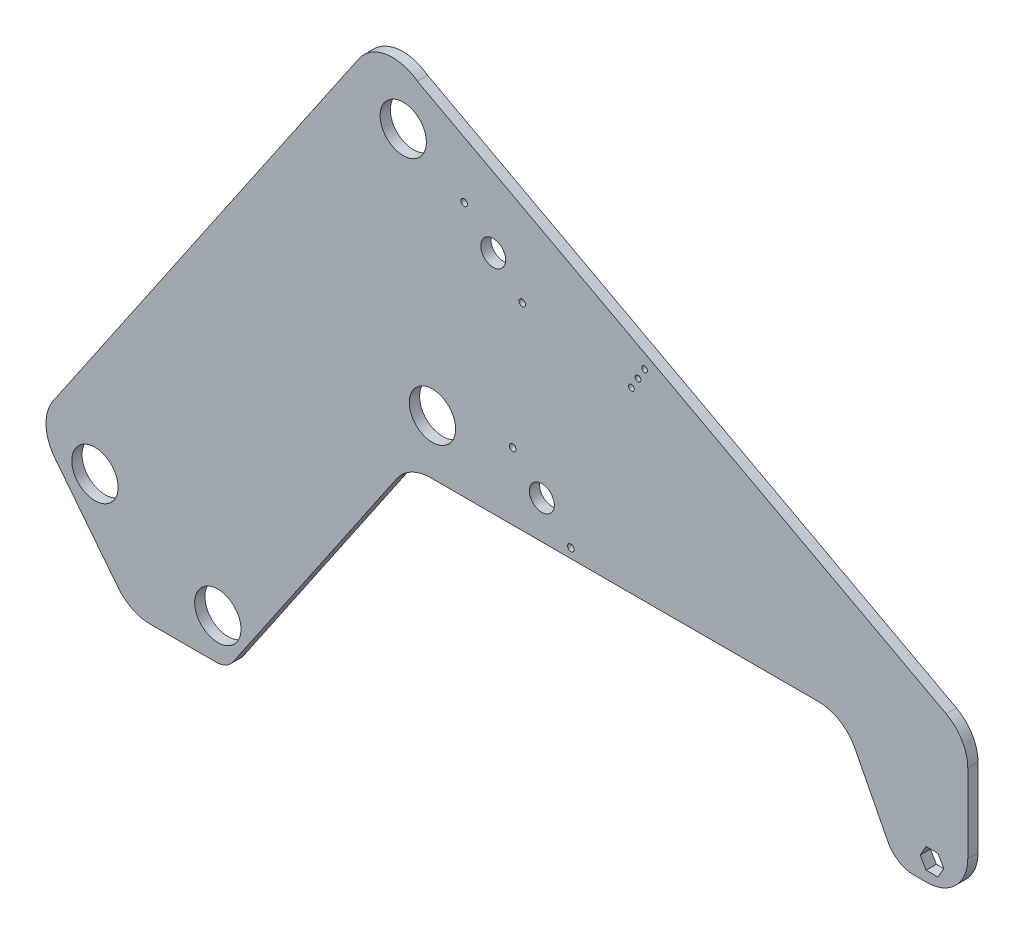
SolidWorks part; units mm, degrees
other "Markup1"
sketch "Sketch1" plane through (-441.7893, 331.8239, 6.35) normal (-0.0431, 0.0102, 0.999) x (0.9985, 0.0354, 0.0427)
sketch "Sketch2" plane through (-413.6701, 343.933, 6.35) normal (-0.0431, 0.0102, 0.999) x (0.9985, 0.0354, 0.0427)
sketch "Sketch3" plane through (-436.3774, 318.5567, 6.35) normal (-0.0431, 0.0102, 0.999) x (0.9985, 0.0354, 0.0427)
sketch "Sketch5" plane through (-436.3774, 318.5567, 6.35) normal (-0.0431, 0.0102, 0.999) x (0.9985, 0.0354, 0.0427)
sketch "Sketch7" plane through (-430.3226, 318.5567, 6.35) normal (-0.0431, 0.0102, 0.999) x (0.9985, 0.0354, 0.0427)
sketch "Sketch9" plane through (-430.3226, 318.5567, 6.35) normal (-0.0431, 0.0102, 0.999) x (0.9985, 0.0354, 0.0427)
sketch "Sketch11" plane through (-430.3226, 318.5567, 6.35) normal (-0.0431, 0.0102, 0.999) x (0.9985, 0.0354, 0.0427)
sketch "Sketch13" plane through (-430.3226, 318.5567, 6.35) normal (-0.0431, 0.0102, 0.999) x (0.9985, 0.0354, 0.0427)
other "Markup2"
sketch "Sketch4" plane through (102.4721, 318.5567, 6.35) normal (0.9364, 0.1073, 0.3342) x (0.3416, -0.0598, -0.9379)
sketch "Sketch6" plane through (102.4721, 318.5567, 6.35) normal (0.9364, 0.1073, 0.3342) x (0.3416, -0.0598, -0.9379)
sketch "Sketch8" plane through (141.2086, 318.5567, 6.35) normal (0.9364, 0.1073, 0.3342) x (0.3416, -0.0598, -0.9379)
sketch "Sketch10" plane through (141.2086, 318.5567, 6.35) normal (0.9364, 0.1073, 0.3342) x (0.3416, -0.0598, -0.9379)
sketch "Sketch12" plane through (141.2086, 318.5567, 6.35) normal (0.9364, 0.1073, 0.3342) x (0.3416, -0.0598, -0.9379)
sketch "Sketch14" plane through (141.2086, 318.5567, 6.35) normal (0.9364, 0.1073, 0.3342) x (0.3416, -0.0598, -0.9379)
material "Lexan"
ref_plane "Front Plane" through (0, 0, 0) normal (0, 0, 1) x (1, 0, 0)
ref_plane "Top Plane" through (0, 0, 0) normal (0, 1, 0) x (1, 0, 0)
ref_plane "Right Plane" through (0, 0, 0) normal (1, 0, 0) x (0, 0, -1)
sketch "Model" plane through (0, 0, 0) normal (0, 0, 1) x (1, 0, 0)
  line L1 (-191.9011, 104.6502) -> (-112.96, 104.6502)
  line L3 (-314.2383, -55.3595) -> (-212.8994, 93.5413)
  line L4 (-236.3088, 307.4396) -> (-425.9253, 28.8296)
  line L5 (-424.901, -1.1522) -> (-385.5815, -51.2048)
  line L13 (126.3831, 53.8502) -> (122.717, 60.2002)
  line L14 (122.717, 60.2002) -> (115.3846, 60.2002)
  line L15 (115.3846, 60.2002) -> (111.7185, 53.8502)
  line L16 (111.7185, 53.8502) -> (115.3846, 47.5002)
  line L17 (115.3846, 47.5002) -> (122.717, 47.5002)
  line L18 (122.717, 47.5002) -> (126.3831, 53.8502)
  line L19 (-365.6075, -60.914) -> (-324.7375, -60.914)
  line L20 (-871.0211, -88.854) -> (370.1019, -88.854) construction
  line L22 (141.2086, 66.5502) -> (141.2086, 78.8846)
  line L27 (107.6196, 41.1502) -> (115.8086, 41.1502)
  line L28 (-399.9752, 2.586) -> (-323.7752, -35.514) construction
  line L29 (-323.7752, -35.514) -> (-190.7071, 138.5169) construction
  line L30 (-190.7071, 138.5169) -> (-208.8329, 283.4378) construction
  line L31 (-208.8329, 283.4378) -> (-399.9752, 2.586) construction
  line L32 (91.8004, 50.8135) -> (71.26, 90.8456)
  line L33 (48.6612, 104.6502) -> (-11.3966, 104.6502)
  line L34 (141.2086, 78.8846) -> (141.2086, 115.3033)
  line L35 (127.8091, 137.6897) -> (-86.3327, 252.4836)
  line L36 (-171.0363, 260.7567) -> (-135.0085, 260.7567) construction
  line L37 (-135.0085, 260.7567) -> (-135.0085, 224.9427)
  line L38 (-171.0363, 260.7567) -> (-135.0085, 224.9427)
  line L39 (-171.0363, 260.7567) -> (-153.0224, 260.7567)
  line L40 (-68.51, 104.6502) -> (-2.1388, 104.6502)
  line L41 (-122.3008, 271.7648) -> (-200.0053, 313.4195)
  line L42 (-122.3008, 271.7648) -> (-86.3327, 252.4836)
  line L43 (-112.96, 104.6502) -> (-68.51, 104.6502)
  line L44 (-153.0224, 260.7567) -> (-153.0224, 244.7547)
  line L45 (-140.9024, 144.2514) -> (-104.8747, 144.2514) construction
  line L46 (-104.8747, 144.2514) -> (-104.8747, 108.4374)
  line L47 (-140.9024, 144.2514) -> (-104.8747, 108.4374)
  line L48 (-140.9024, 144.2514) -> (-122.8885, 144.2514)
  line L49 (-122.8885, 144.2514) -> (-122.8885, 128.2494)
  line L50 (-200.0053, 313.4195) -> (-58.2414, 230.7964)
  line L51 (-58.2414, 230.7964) -> (-55.4813, 235.9452)
  line L52 (-60.5805, 226.7863) -> (-58.2414, 230.7964)
  arc A3 (121.2475, 59.8082) -> (121.352, 60.2002) centre (96.7586, 66.5502) ccw
  circle A9 centre (-323.7752, -35.514) radius 14.351
  circle A10 centre (-399.9752, 2.586) radius 14.351
  circle A12 centre (-190.7071, 138.5169) radius 14.351
  arc A15 (107.6196, 41.1502) -> (91.8004, 50.8135) centre (107.6196, 58.9302) cw
  arc A21 (-191.9011, 104.6502) -> (-212.8994, 93.5413) centre (-191.9011, 79.2502) ccw
  circle A22 centre (-208.8329, 283.4378) radius 14.351
  circle A24 centre (119.0508, 53.8502) radius 6.35 construction
  arc A31 (-324.7375, -60.914) -> (-314.2383, -55.3595) centre (-324.7375, -48.214) ccw
  arc A40 (114.7422, 48.6129) -> (115.0458, 48.9225) centre (96.7586, 66.5502) ccw
  arc A43 (115.8086, 41.1502) -> (141.2086, 66.5502) centre (115.8086, 66.5502) ccw
  arc A44 (-236.3088, 307.4396) -> (-200.0053, 313.4195) centre (-215.3105, 293.1486) cw
  arc A45 (-365.6075, -60.914) -> (-385.5815, -51.2048) centre (-365.6075, -35.514) cw
  arc A46 (71.26, 90.8456) -> (48.6612, 104.6502) centre (48.6612, 79.2502) ccw
  arc A47 (141.2086, 115.3033) -> (127.8091, 137.6897) centre (115.8086, 115.3033) ccw
  arc A48 (-424.901, -1.1522) -> (-425.9253, 28.8296) centre (-404.9271, 14.5386) cw
  circle A51 centre (-171.0363, 262.7887) radius 2.032
  circle A52 centre (-135.0085, 226.9747) radius 2.032
  circle A53 centre (-153.0224, 244.7547) radius 7.747
  circle A54 centre (-140.9024, 146.2834) radius 2.032
  circle A55 centre (-104.8747, 110.4694) radius 2.032
  circle A56 centre (-122.8885, 128.2494) radius 7.747
  circle A57 centre (-59.1373, 229.2606) radius 1.778
  circle A60 centre (-63.2326, 222.2397) radius 1.778
  circle A61 centre (-67.3279, 215.2188) radius 1.778
  ellipse E0 centre (-551.1692, 173.9527) end of major axis (-591.2054, 216.0961) minor radius 17.278
  point P31 (-177.5612, 330.9695)
  point P34 (100.2935, -12.8222)
  point P43 (-377.9543, -60.914)
  point P55 (96.7586, 41.1502)
  point P59 (174.831, 53.8502)
  point P60 (-205.3388, 104.6502)
  point P64 (-436.3829, 13.4639)
  dimension "D3" = 38.1
  dimension "D4" = 104.6502
  dimension "D5" = 76.2
  dimension "D6" = 44.45
  dimension "D7" = 12.7
  dimension "D8" = 28.702
  dimension "D11" = 139.7
  dimension "D12" = 27.94
  dimension "D21" = 124.238
  dimension "D13" = 12.7
  dimension "D16" = 355.6
  dimension "D23" = 25.4
  dimension "D24" = 25.4
  dimension "D26" = 25.4
  dimension "D14" = 406.4
  dimension "D20" = 254
  dimension "D29" = 25.4
  dimension "D31" = 25.4
  dimension "D25" = 88.9
  dimension "D30" = 17.78
  dimension "D32" = 25.4
  dimension "D33" = 25.4
  dimension "D34" = 35.814
  dimension "D35" = 50.8
  dimension "D37" = 4.064
  dimension "D38" = 4.064
  dimension "D39" = 15.494
  dimension "D42" = 4.064
  dimension "D43" = 15.494
  dimension "D44" = 4.064
  dimension "D48" = 3.556
  dimension "D9" = 19.05
  dimension "D10" = 146.05
  dimension "D15" = 33.8667
  dimension "D17" = 339.725
  dimension "D18" = 219.075
  dimension "D19" = 50.8
  dimension "D22" = 25.4
  dimension "D27" = 53.2168
  dimension "D28" = 12.7
  dimension "D36" = 16.002
  dimension "D40" = 35.814
  dimension "D41" = 16.002
  dimension "D45" = 50.8
  dimension "D46" = 164.084
  dimension "D47" = 5.842
  dimension "D49" = 3
extrude "Boss-Extrude1" add sketch "Model" along normal blind 6.35 contours A48 L5 A45 L19 A31 L3 A21 L1 L43 L40 L33 A46 L32 A15 L27 A43 L22 L34 A47 L35 L42 L41 A44 L4 A56 L47 A54 L48 L49 A55 A53 L38 A51 L39 L44 A52 | A56 L49 L48 L47 | A53 L44 L39 L38 | L50 L51 L42 L41 region at (-206.9871, 107.7659, 0) region at (-104.576, 260.0537, 0) region at (-160.0611, 256.5181, 0) region at (-129.9272, 140.0129, 0)
